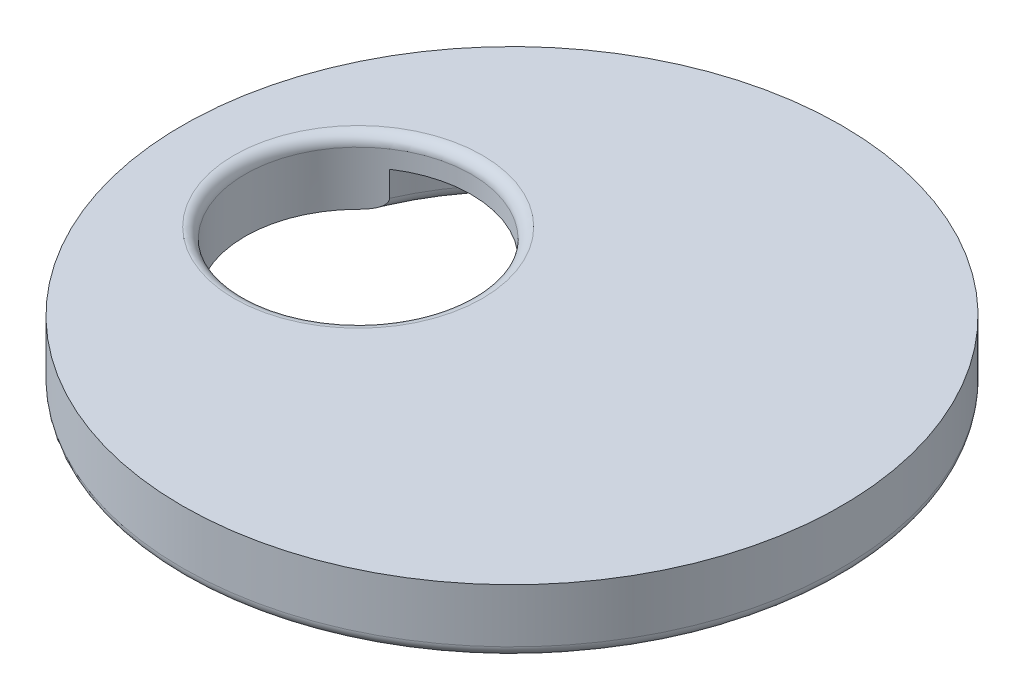
SolidWorks part; units mm, degrees
ref_plane "Front Plane" through (0, 0, 0) normal (0, 0, 1) x (1, 0, 0)
ref_plane "Top Plane" through (0, 0, 0) normal (0, 1, 0) x (1, 0, 0)
ref_plane "Right Plane" through (0, 0, 0) normal (1, 0, 0) x (0, 0, -1)
sketch "Sketch1" plane through (0, 0, 0) normal (0, 1, 0) x (1, 0, 0)
  line L0 (0, 0) -> (-15, 0) construction
  circle A0 centre (0, 0) radius 15
  circle A2 centre (-7, 0) radius 5.15
  circle A3 centre (0, 0) radius 10.75
  dimension "D1" = 30
  dimension "D2" = 8
  dimension "D3" = 10.3
  dimension "D4" = 21.5
extrude "Boss-Extrude1" add sketch "Sketch1" along normal blind 1.3 contours A2 A3 | A3 A2 A0 region at (-14.5757, 0, 0) region at (1.6875, 0, 0)
extrude "Boss-Extrude2" add sketch "Sketch1<3>" against normal blind 1.65 contours A0 | A3
sketch "Sketch1<3>" plane through (0, 0, 0) normal (0, 1, 0) x (1, 0, 0) same geometry as "Sketch1"
extrude "Cut-Extrude1" cut sketch "Sketch1<4>" against normal blind 1.65 contours L0 A3 A2 | A3 L0 A2 region at (-11.1382, 0, 1.6981) region at (-11.1382, 0, -1.6981)
sketch "Sketch1<4>" plane through (0, 0, 0) normal (0, 1, 0) x (1, 0, 0) same geometry as "Sketch1"
fillet "Fillet5" radius 0.5 1 edges at (-7, 1.3, 5.15)
fillet "Fillet6" radius 0.5 2 edges at (10.75, -1.65, 0) (0, -1.65, 15)
